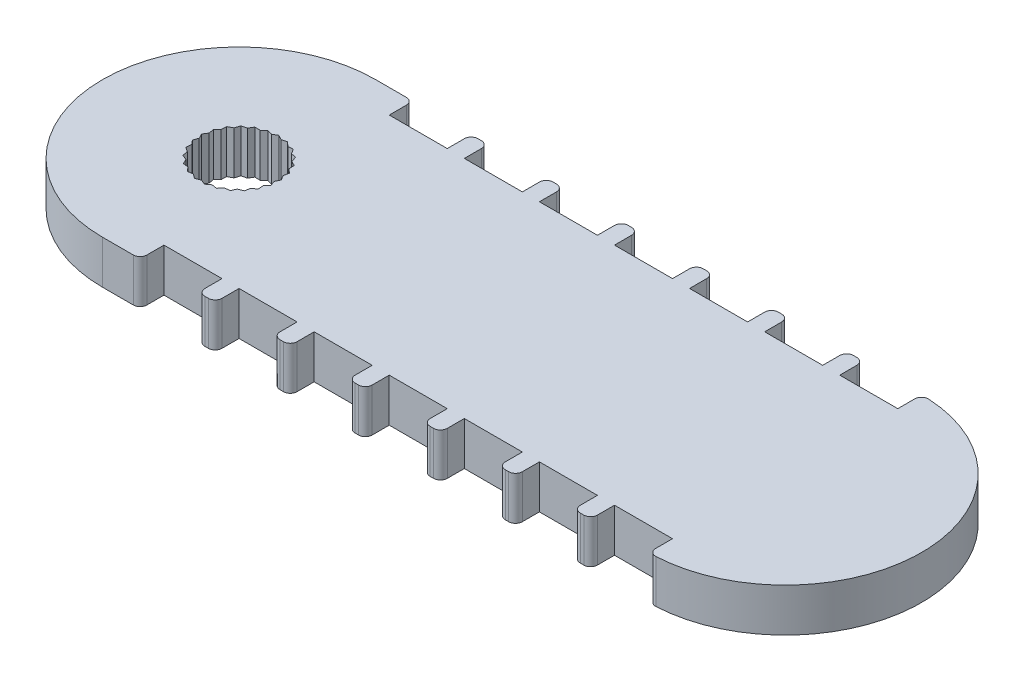
SolidWorks part; units mm, degrees
ref_plane "Front Plane" through (0, 0, 0) normal (0, 0, 1) x (1, 0, 0)
ref_plane "Top Plane" through (0, 0, 0) normal (0, 1, 0) x (1, 0, 0)
ref_plane "Right Plane" through (0, 0, 0) normal (1, 0, 0) x (0, 0, -1)
sketch "Sketch1" plane through (0, 0, 0) normal (0, 1, 0) x (1, 0, 0)
  line L0 (0, 2.925) -> (-0.3447, 2.7283)
  line L1 (0, 2.925) -> (0.3447, 2.7283)
  line L2 (0.7274, 2.8331) -> (0.3447, 2.7283)
  line L3 (0.7274, 2.8331) -> (1.0123, 2.5569)
  line L4 (1.4091, 2.5632) -> (1.0123, 2.5569)
  line L5 (1.4091, 2.5632) -> (1.6164, 2.2248)
  line L6 (2.0023, 2.1322) -> (1.6164, 2.2248)
  line L7 (2.0023, 2.1322) -> (2.1189, 1.7529)
  line L8 (2.4697, 1.5673) -> (2.1189, 1.7529)
  line L9 (2.4697, 1.5673) -> (2.4883, 1.1709)
  line L10 (2.7818, 0.9039) -> (2.4883, 1.1709)
  line L11 (2.7818, 0.9039) -> (2.7013, 0.5153)
  line L12 (2.9192, 0.1837) -> (2.7013, 0.5153)
  line L13 (2.9192, 0.1837) -> (2.7446, -0.1727)
  line L14 (2.8732, -0.5481) -> (2.7446, -0.1727)
  line L15 (2.8732, -0.5481) -> (2.6154, -0.8498)
  line L16 (2.6466, -1.2454) -> (2.6154, -0.8498)
  line L17 (2.6466, -1.2454) -> (2.3219, -1.4735)
  line L18 (2.2538, -1.8645) -> (2.3219, -1.4735)
  line L19 (2.2538, -1.8645) -> (1.8825, -2.0047)
  line L20 (1.7193, -2.3664) -> (1.8825, -2.0047)
  line L21 (1.7193, -2.3664) -> (1.3248, -2.4098)
  line L22 (1.0768, -2.7196) -> (1.3248, -2.4098)
  line L23 (1.0768, -2.7196) -> (0.6839, -2.6636)
  line L24 (0.3666, -2.9019) -> (0.6839, -2.6636)
  line L25 (0.3666, -2.9019) -> (0, -2.75)
  line L26 (-0.3666, -2.9019) -> (0, -2.75)
  line L27 (-0.3666, -2.9019) -> (-0.6839, -2.6636)
  line L28 (-1.0768, -2.7196) -> (-0.6839, -2.6636)
  line L29 (-1.0768, -2.7196) -> (-1.3248, -2.4098)
  line L30 (-1.7193, -2.3664) -> (-1.3248, -2.4098)
  line L31 (-1.7193, -2.3664) -> (-1.8825, -2.0047)
  line L32 (-2.2538, -1.8645) -> (-1.8825, -2.0047)
  line L33 (-2.2538, -1.8645) -> (-2.3219, -1.4735)
  line L34 (-2.6466, -1.2454) -> (-2.3219, -1.4735)
  line L35 (-2.6466, -1.2454) -> (-2.6154, -0.8498)
  line L36 (-2.8732, -0.5481) -> (-2.6154, -0.8498)
  line L37 (-2.8732, -0.5481) -> (-2.7446, -0.1727)
  line L38 (-2.9192, 0.1837) -> (-2.7446, -0.1727)
  line L39 (-2.9192, 0.1837) -> (-2.7013, 0.5153)
  line L40 (-2.7818, 0.9039) -> (-2.7013, 0.5153)
  line L41 (-2.7818, 0.9039) -> (-2.4883, 1.1709)
  line L42 (-2.4697, 1.5673) -> (-2.4883, 1.1709)
  line L43 (-2.4697, 1.5673) -> (-2.1189, 1.7529)
  line L44 (-2.0023, 2.1322) -> (-2.1189, 1.7529)
  line L45 (-2.0023, 2.1322) -> (-1.6164, 2.2248)
  line L46 (-1.4091, 2.5632) -> (-1.6164, 2.2248)
  line L47 (-1.4091, 2.5632) -> (-1.0123, 2.5569)
  line L48 (-0.7274, 2.8331) -> (-1.0123, 2.5569)
  line L49 (-0.7274, 2.8331) -> (-0.3447, 2.7283)
  line L50 (0, 10) -> (2.75, 10)
  line L51 (0, -10) -> (2.75, -10)
  line L52 (0, 0) -> (40, 0) construction
  line L53 (40, 10) -> (40, 8.25)
  line L54 (40, 8.25) -> (35.75, 8.25)
  line L55 (35.75, 8.25) -> (35.75, 10)
  line L56 (30.25, 8.25) -> (30.25, 10)
  line L57 (34.5, 8.25) -> (30.25, 8.25)
  line L58 (34.5, 10) -> (34.5, 8.25)
  line L59 (24.75, 8.25) -> (24.75, 10)
  line L60 (29, 8.25) -> (24.75, 8.25)
  line L61 (29, 10) -> (29, 8.25)
  line L62 (19.25, 8.25) -> (19.25, 10)
  line L63 (23.5, 8.25) -> (19.25, 8.25)
  line L64 (23.5, 10) -> (23.5, 8.25)
  line L65 (13.75, 8.25) -> (13.75, 10)
  line L66 (18, 8.25) -> (13.75, 8.25)
  line L67 (18, 10) -> (18, 8.25)
  line L68 (8.25, 8.25) -> (8.25, 10)
  line L69 (12.5, 8.25) -> (8.25, 8.25)
  line L70 (12.5, 10) -> (12.5, 8.25)
  line L71 (2.75, 8.25) -> (2.75, 10)
  line L72 (7, 8.25) -> (2.75, 8.25)
  line L73 (7, 10) -> (7, 8.25)
  line L74 (35.75, 8.25) -> (30.25, 8.25) construction
  line L75 (35.75, -8.25) -> (30.25, -8.25) construction
  line L76 (7, -10) -> (7, -8.25)
  line L77 (7, -8.25) -> (2.75, -8.25)
  line L78 (2.75, -8.25) -> (2.75, -10)
  line L79 (12.5, -10) -> (12.5, -8.25)
  line L80 (12.5, -8.25) -> (8.25, -8.25)
  line L81 (8.25, -8.25) -> (8.25, -10)
  line L82 (18, -10) -> (18, -8.25)
  line L83 (18, -8.25) -> (13.75, -8.25)
  line L84 (13.75, -8.25) -> (13.75, -10)
  line L85 (23.5, -10) -> (23.5, -8.25)
  line L86 (23.5, -8.25) -> (19.25, -8.25)
  line L87 (19.25, -8.25) -> (19.25, -10)
  line L88 (29, -10) -> (29, -8.25)
  line L89 (29, -8.25) -> (24.75, -8.25)
  line L90 (24.75, -8.25) -> (24.75, -10)
  line L91 (34.5, -10) -> (34.5, -8.25)
  line L92 (34.5, -8.25) -> (30.25, -8.25)
  line L93 (30.25, -8.25) -> (30.25, -10)
  line L94 (35.75, -8.25) -> (35.75, -10)
  line L95 (40, -8.25) -> (35.75, -8.25)
  line L96 (40, -10) -> (40, -8.25)
  line L97 (7, 10) -> (8.25, 10)
  line L98 (12.5, 10) -> (13.75, 10)
  line L99 (18, 10) -> (19.25, 10)
  line L100 (23.5, 10) -> (24.75, 10)
  line L101 (29, 10) -> (30.25, 10)
  line L102 (34.5, 10) -> (35.75, 10)
  line L103 (34.5, -10) -> (35.75, -10)
  line L104 (29, -10) -> (30.25, -10)
  line L105 (23.5, -10) -> (24.75, -10)
  line L106 (18, -10) -> (19.25, -10)
  line L107 (12.5, -10) -> (13.75, -10)
  line L108 (7, -10) -> (8.25, -10)
  circle A0 centre (0, 0) radius 2.925 construction
  circle A1 centre (0, 0) radius 2.75 construction
  arc A2 (0, 10) -> (0, -10) centre (0, 0) ccw
  arc A3 (40, -10) -> (40, 10) centre (40, 0) ccw
  point P82 (0, 0)
  dimension "D1" = 5.85
  dimension "D2" = 5.5
  dimension "D4" = 20
  dimension "D5" = 40
  dimension "D6" = 4.25
  dimension "D7" = 1.75
  dimension "D9" = 5.5
  dimension "D8" = 7
  dimension "D3" = 25
extrude "Boss-Extrude1" add sketch "Sketch1" along normal blind 3.175
fillet "Fillet1" radius 0.5 28 edges at (8.25, 1.5875, -10) (7, 1.5875, -10) (2.75, 1.5875, -10) (2.75, 1.5875, 10) (7, 1.5875, 10) (8.25, 1.5875, 10) (12.5, 1.5875, 10) (13.75, 1.5875, 10) (18, 1.5875, 10) (19.25, 1.5875, 10) (23.5, 1.5875, 10) (24.75, 1.5875, 10) (29, 1.5875, 10) (30.25, 1.5875, 10) (34.5, 1.5875, 10) (35.75, 1.5875, 10) (40, 1.5875, 10) (40, 1.5875, -10) (35.75, 1.5875, -10) (34.5, 1.5875, -10) (30.25, 1.5875, -10) (29, 1.5875, -10) (24.75, 1.5875, -10) (23.5, 1.5875, -10) (19.25, 1.5875, -10) (18, 1.5875, -10) (13.75, 1.5875, -10) (12.5, 1.5875, -10)
